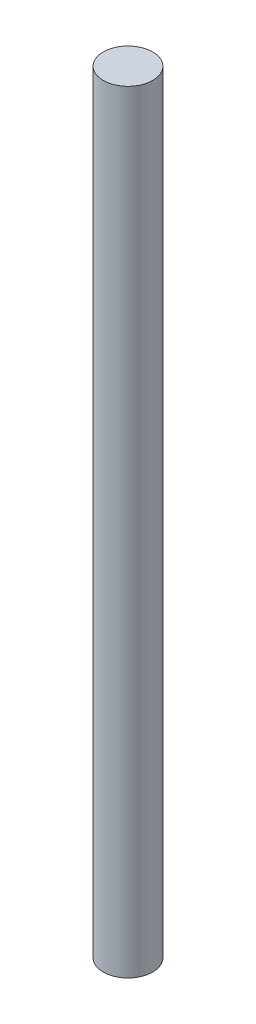
SolidWorks part; units mm, degrees
ref_plane "Front Plane" through (0, 0, 0) normal (0, 0, 1) x (1, 0, 0)
ref_plane "Top Plane" through (0, 0, 0) normal (0, 1, 0) x (1, 0, 0)
ref_plane "Right Plane" through (0, 0, 0) normal (1, 0, 0) x (0, 0, -1)
sketch "Sketch1" plane through (0, 0, 0) normal (0, 1, 0) x (1, 0, 0)
  circle A0 centre (0, 0) radius 4
  dimension "D1" = 8
extrude "Boss-Extrude1" add sketch "Sketch1" along normal blind 125
